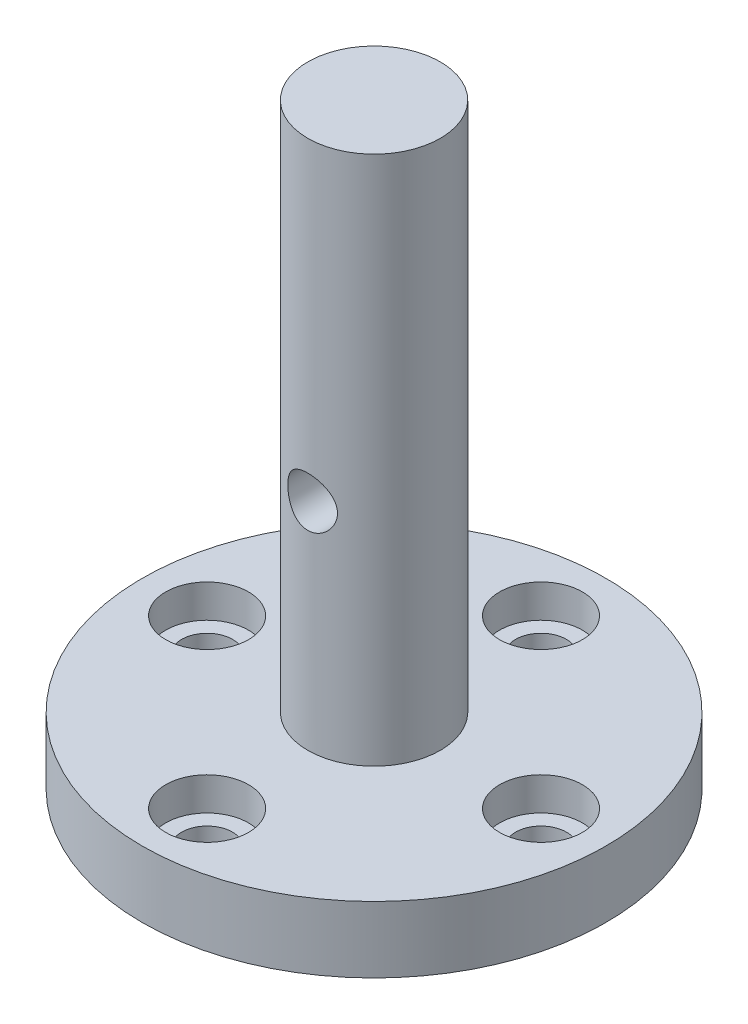
SolidWorks part; units mm, degrees
material "6061-T6 (SS)"
ref_plane "Front Plane" through (0, 0, 0) normal (0, 0, 1) x (1, 0, 0)
ref_plane "Top Plane" through (0, 0, 0) normal (0, 1, 0) x (1, 0, 0)
ref_plane "Right Plane" through (0, 0, 0) normal (1, 0, 0) x (0, 0, -1)
sketch "Sketch1" plane through (0, 0, 0) normal (0, 1, 0) x (1, 0, 0)
  circle A0 centre (0, 0) radius 11.1125
  circle A1 centre (0, 0) radius 3.175 construction
  circle A2 centre (0, 0) radius 8 construction
  dimension "D1" = 6.35
  dimension "D2" = 16
  dimension "D3" = 22.225
extrude "Boss-Extrude1" add sketch "Sketch1" along normal blind 3.175
sketch "Sketch2" plane through (0, 3.175, 0) normal (0, 1, 0) x (1, 0, 0)
  circle A0 centre (0, 0) radius 3.175
  dimension "D1" = 6.35
extrude "Boss-Extrude2" add sketch "Sketch2" along normal blind 25.4
hole_wizard "#2 Clearance Hole1" positions "Sketch3" profile "Sketch4" hole size "#2" standard "ANSI Inch" end condition through all
sketch "Sketch3" plane through (0, 3.175, 0) normal (0, 1, 0) x (1, 0, 0)
  circle A0 centre (0, 0) radius 8
  point P0 (0, -8)
  point P2 (0, 8)
  point P4 (-8, 0)
  point P6 (8, 0)
  dimension "D1" = 16
sketch "Sketch4" plane through (0, 3.175, 8) normal (1, 0, 0) x (0, 0, 1)
  line L0 (0, 0) -> (0, 3.175)
  line L1 (0, 3.175) -> (1.2192, 3.175)
  line L2 (1.2192, 3.175) -> (1.2192, 0)
  line L5 (1.2192, 0) -> (0, 0)
  line L11 (0, -6.35) -> (0, 107.95) construction
  dimension "Thru Hole Dia." = 2.4384
  dimension "Thru Hole Depth" = 3.175
sketch "Sketch5" plane through (0, 3.175, 0) normal (0, 1, 0) x (1, 0, 0)
  circle A0 centre (0, -8) radius 1.9844
  circle A1 centre (8, 0) radius 1.9844
  circle A2 centre (0, 8) radius 1.9844
  circle A3 centre (-8, 0) radius 1.9844
  dimension "D1" = 3.9688
extrude "Cut-Extrude1" cut sketch "Sketch5" against normal blind 1.5875
ref_plane "Plane1" through (0, 0, 3.175) normal (0, 0, 1) x (1, 0, 0)
hole_wizard "3/32 (0.09375) Diameter Hole1" positions "Sketch7" profile "Sketch8" hole size "3/32" standard "ANSI Inch" end condition through all
sketch "Sketch7" plane through (0, 0, 3.175) normal (0, 0, 1) x (1, 0, 0)
  line L0 (3.175, 3.175) -> (-3.175, 3.175) construction
  line L1 (3.175, 3.175) -> (-3.175, 3.175) construction
  line L2 (3.175, 28.575) -> (-3.175, 28.575) construction
  line L3 (3.175, 28.575) -> (-3.175, 28.575) construction
  line L4 (0, 28.575) -> (0, 3.175) construction
  point P0 (0, 13.4938)
  point P20 (0, 15.875)
  dimension "D1" = 2.3812
sketch "Sketch8" plane through (0, 13.4938, 3.175) normal (1, 0, 0) x (0, -1, 0)
  line L0 (0, 0) -> (0, 14.2875)
  line L1 (0, 14.2875) -> (1.1906, 14.2875)
  line L2 (1.1906, 14.2875) -> (1.1906, 0)
  line L5 (1.1906, 0) -> (0, 0)
  line L11 (0, -6.35) -> (0, 107.95) construction
  dimension "Thru Hole Dia." = 2.3812
  dimension "Thru Hole Depth" = 14.2875
